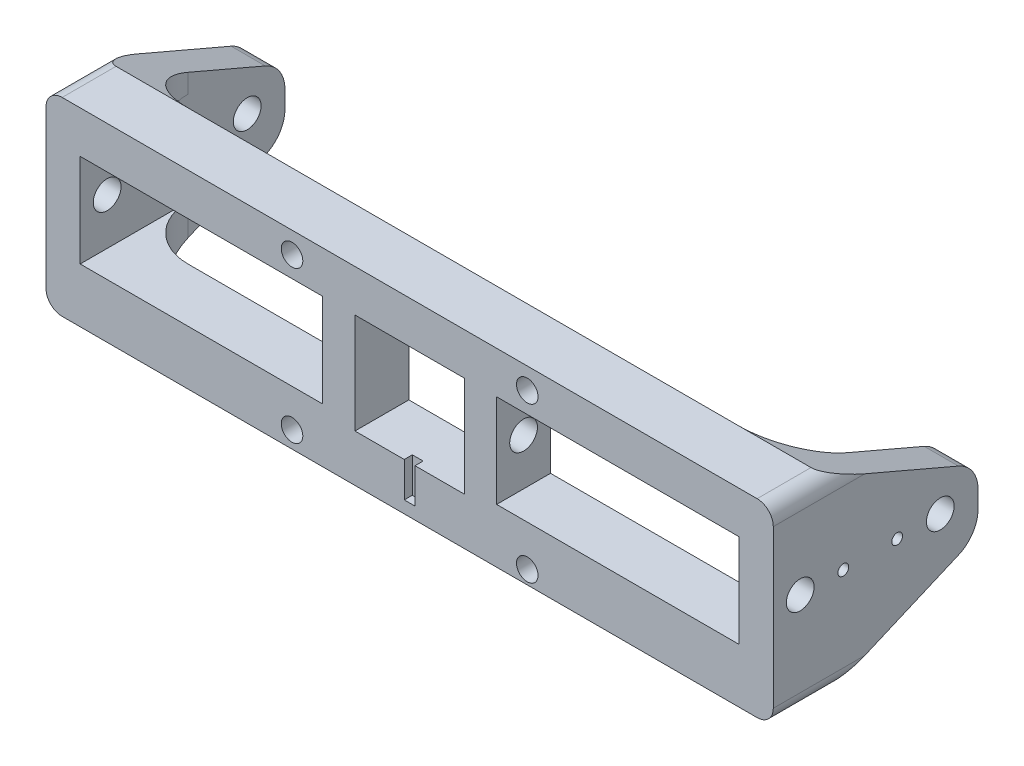
SolidWorks part; units mm, degrees
material "Vero PureWhite"
ref_plane "前视基准面" through (0, 0, 0) normal (0, 0, 1) x (1, 0, 0)
ref_plane "上视基准面" through (0, 0, 0) normal (0, 1, 0) x (1, 0, 0)
ref_plane "右视基准面" through (0, 0, 0) normal (1, 0, 0) x (0, 0, -1)
sketch "草图1" plane through (0, 0, 0) normal (0, 0, 1) x (1, 0, 0)
  line L1 (-67.5, 29) -> (67.5, 29)
  line L2 (-67.5, 29) -> (-67.5, -29)
  line L3 (-67.5, -29) -> (67.5, -29)
  line L4 (67.5, 29) -> (67.5, -29)
  line L5 (-67.5, 29) -> (67.5, -29) construction
  line L6 (-67.5, -29) -> (67.5, 29) construction
  point P0 (0, 0)
  dimension "D1" = 135
  dimension "D2" = 58
extrude "凸台-拉伸1" add sketch "草图1" along normal blind 10
sketch "草图3" plane through (0, 0, 0) normal (0, 0, -1) x (-1, 0, 0)
  line L1 (-10.15, 20.25) -> (10.15, 20.25)
  line L2 (-10.15, 20.25) -> (-10.15, -20.25)
  line L3 (-10.15, -20.25) -> (10.15, -20.25)
  line L4 (10.15, 20.25) -> (10.15, -20.25)
  line L5 (-10.15, 20.25) -> (10.15, -20.25) construction
  line L6 (-10.15, -20.25) -> (10.15, 20.25) construction
  point P0 (0, 0)
  dimension "D1" = 40.5
  dimension "D2" = 20.3
extrude "切除-拉伸1" cut sketch "草图3" against normal blind 20
sketch "草图4" plane through (0, 0, 0) normal (0, 0, -1) x (-1, 0, 0)
  line L0 (0, 0) -> (0, 8.0602) construction
  line L1 (0, 0) -> (3.3984, 0) construction
  circle A0 centre (-5, 24.6) radius 1.525
  circle A1 centre (5, 24.6) radius 1.525
  circle A2 centre (5, -24.6) radius 1.525
  circle A3 centre (-5, -24.6) radius 1.525
  dimension "D1" = 3.05
  dimension "D2" = 5
  dimension "D3" = 24.6
extrude "切除-拉伸2" cut sketch "草图4" against normal blind 20
sketch "草图5" plane through (0, 0, 0) normal (0, 0, -1) x (-1, 0, 0)
  line L0 (-10.15, -20.25) -> (10.15, -20.25) construction
  line L1 (10.15, -20.25) -> (10.15, 20.25) construction
  line L2 (61.15, -17.9) -> (16.15, -17.9)
  line L3 (61.15, -17.9) -> (61.15, -2.6)
  line L4 (61.15, -2.6) -> (16.15, -2.6)
  line L5 (16.15, -17.9) -> (16.15, -2.6)
  line L6 (61.15, -17.9) -> (16.15, -2.6) construction
  line L7 (61.15, -2.6) -> (16.15, -17.9) construction
  line L9 (0, 0) -> (0, -4.0519) construction
  line L10 (-61.15, -2.6) -> (-16.15, -17.9) construction
  line L11 (-61.15, -17.9) -> (-16.15, -2.6) construction
  line L12 (-16.15, -17.9) -> (-16.15, -2.6)
  line L13 (-61.15, -2.6) -> (-16.15, -2.6)
  line L14 (-61.15, -17.9) -> (-61.15, -2.6)
  line L15 (-61.15, -17.9) -> (-16.15, -17.9)
  point P0 (2.5, -10.25)
  point P3 (38.65, -10.25)
  point P17 (-38.65, -10.25)
  dimension "D1" = 10
  dimension "D2" = 45
  dimension "D3" = 6
  dimension "D4" = 15.3
extrude "切除-拉伸3" cut sketch "草图5" against normal blind 20
sketch "草图7" plane through (-67.5, 0, 0) normal (-1, 0, 0) x (0, 0, 1)
  line L0 (10, -17.9) -> (0, -17.9) construction
  line L1 (0, -17.9) -> (0, -2.6) construction
  line L2 (10, -17.9) -> (10, -2.6) construction
  line L3 (10, -2.6) -> (0, -2.6) construction
  line L4 (10, -17.9) -> (0, -17.9) construction
  line L5 (0, -17.9) -> (0, -2.6) construction
  line L6 (10, -17.9) -> (10, -2.6) construction
  line L7 (10, -2.6) -> (0, -2.6) construction
  circle A0 centre (5, -10.25) radius 2.575
  point P6 (5, -2.6)
  point P7 (10, -10.25)
  dimension "D1" = 5.15
extrude "切除-拉伸4" cut sketch "草图7" against normal blind 57
sketch "草图9" plane through (0, 0, 0) normal (0, 0, -1) x (-1, 0, 0)
  line L0 (-16.15, -2.6) -> (-61.15, -2.6) construction
  line L1 (-67.5, 29) -> (-18.15, 29)
  line L2 (-67.5, 29) -> (-67.5, 6.2)
  line L3 (-67.5, 6.2) -> (-18.15, 6.2)
  line L4 (-18.15, 29) -> (-18.15, 6.2)
  line L5 (-10.15, 20.25) -> (-10.15, -20.25) construction
  line L6 (0, 5.5) -> (0, -5.5) construction
  line L7 (18.15, 29) -> (18.15, 6.2)
  line L8 (67.5, 6.2) -> (18.15, 6.2)
  line L9 (67.5, 29) -> (67.5, 6.2)
  line L10 (67.5, 29) -> (18.15, 29)
  dimension "D1" = 8.8
  dimension "D2" = 8
extrude "切除-拉伸6" cut sketch "草图9" against normal blind 48
fillet "圆角1" radius 3 4 edges at (-18.15, 6.2, 5) (-18.15, 29, 5) (18.15, 6.2, 5) (18.15, 29, 5)
fillet "圆角2" radius 3 4 edges at (-67.5, 6.2, 5) (-67.5, -29, 5) (67.5, 6.2, 5) (67.5, -29, 5)
sketch "草图10" plane through (67.5, 0, 0) normal (1, 0, 0) x (0, 0, -1)
  circle A0 centre (-5, -10.25) radius 2.575 construction
  circle A1 centre (-5, -10.25) radius 2.575
extrude "切除-拉伸7" cut sketch "草图10" against normal blind 57
sketch "草图11" plane through (0, 0, 0) normal (0, 0, -1) x (-1, 0, 0)
  line L0 (61.15, 6.2) -> (61.15, -29)
  line L1 (-61.15, 6.2) -> (-61.15, -29)
  line L2 (61.15, -29) -> (64.5, -29)
  line L8 (67.5, -26) -> (67.5, 3.2)
  line L9 (64.5, 6.2) -> (21.15, 6.2)
  line L10 (18.15, 9.2) -> (18.15, 26)
  line L11 (15.15, 29) -> (-15.15, 29)
  line L12 (-18.15, 26) -> (-18.15, 9.2)
  line L13 (-21.15, 6.2) -> (-64.5, 6.2)
  line L14 (-67.5, 3.2) -> (-67.5, -26)
  line L15 (-64.5, -29) -> (64.5, -29)
  line L16 (67.5, -26) -> (67.5, 3.2)
  line L17 (64.5, 6.2) -> (61.15, 6.2)
  line L21 (-61.15, 6.2) -> (-64.5, 6.2)
  line L22 (-67.5, 3.2) -> (-67.5, -26)
  line L23 (-64.5, -29) -> (-61.15, -29)
  arc A8 (67.5, 3.2) -> (64.5, 6.2) centre (64.5, 3.2) ccw
  arc A9 (18.15, 9.2) -> (21.15, 6.2) centre (21.15, 9.2) ccw
  arc A10 (18.15, 26) -> (15.15, 29) centre (15.15, 26) ccw
  arc A11 (-15.15, 29) -> (-18.15, 26) centre (-15.15, 26) ccw
  arc A12 (-21.15, 6.2) -> (-18.15, 9.2) centre (-21.15, 9.2) ccw
  arc A13 (-64.5, 6.2) -> (-67.5, 3.2) centre (-64.5, 3.2) ccw
  arc A14 (-67.5, -26) -> (-64.5, -29) centre (-64.5, -26) ccw
  arc A15 (64.5, -29) -> (67.5, -26) centre (64.5, -26) ccw
  arc A16 (67.5, 3.2) -> (64.5, 6.2) centre (64.5, 3.2) ccw
  arc A21 (-64.5, 6.2) -> (-67.5, 3.2) centre (-64.5, 3.2) ccw
  arc A22 (-67.5, -26) -> (-64.5, -29) centre (-64.5, -26) ccw
  arc A23 (64.5, -29) -> (67.5, -26) centre (64.5, -26) ccw
  dimension "D1" = 0
extrude "凸台-拉伸2" add sketch "草图11" along normal blind 28
sketch "草图12" plane through (-67.5, 0, 0) normal (-1, 0, 0) x (0, 0, 1)
  line L0 (5, -10.25) -> (-21, -10.25) construction
  circle A0 centre (5, -10.25) radius 2.575 construction
  circle A1 centre (5, -10.25) radius 2.575 construction
  circle A2 centre (-21, -10.25) radius 2.575
  dimension "D1" = 26
extrude "切除-拉伸8" cut sketch "草图12" against normal blind 145
sketch "草图13" plane through (-67.5, 0, 0) normal (-1, 0, 0) x (0, 0, 1)
  line L0 (-28, 6.2) -> (-28, -5.8)
  line L1 (-28, -26) -> (-28, 3.2) construction
  line L2 (-28, -5.8) -> (0, 6.2)
  line L3 (0, 6.2) -> (-28, 6.2)
  line L4 (-28, -11.4) -> (-11.8081, -11.4) construction
  line L5 (0, -29) -> (-28, -29)
  line L6 (-28, -17) -> (0, -29)
  line L7 (-28, -29) -> (-28, -17)
  dimension "D1" = 12
  dimension "D2" = 28
extrude "切除-拉伸9" cut sketch "草图13" against normal blind 145
fillet "圆角3" radius 6 4 edges at (-64.325, -17, -28) (-64.325, -5.8, -28) (64.325, -17, -28) (64.325, -5.8, -28)
fillet "圆角4" radius 10 4 edges at (-61.15, -23.45, 0) (-61.15, 1.8, 0) (61.15, -23.45, 0) (61.15, 1.8, 0)
sketch "草图14" plane through (-67.5, 0, 0) normal (-1, 0, 0) x (0, 0, 1)
  circle A0 centre (-13, -10.25) radius 1
  circle A1 centre (-3, -10.25) radius 1
  circle A2 centre (5, -10.25) radius 2.575 construction
  circle A3 centre (-21, -10.25) radius 2.575 construction
  dimension "D4" = 2
  dimension "D1" = 8
  dimension "D2" = 8
  dimension "D3" = 10
extrude "切除-拉伸10" cut sketch "草图14" against normal blind 135
sketch "草图15" plane through (0, 0, 10) normal (0, 0, 1) x (1, 0, 0)
  line L0 (10.15, 20.25) -> (-10.15, 20.25) construction
  line L1 (-1, 26.75) -> (1, 26.75)
  line L2 (-1, 26.75) -> (-1, 13.75)
  line L3 (-1, 13.75) -> (1, 13.75)
  line L4 (1, 26.75) -> (1, 13.75)
  line L5 (-1, 26.75) -> (1, 13.75) construction
  line L6 (-1, 13.75) -> (1, 26.75) construction
  line L7 (20.9, 0) -> (-20.9, 0) construction
  line L8 (-1, -13.75) -> (1, -26.75) construction
  line L9 (-1, -26.75) -> (1, -13.75) construction
  line L10 (1, -26.75) -> (1, -13.75)
  line L11 (-1, -13.75) -> (1, -13.75)
  line L12 (-1, -26.75) -> (-1, -13.75)
  line L13 (-1, -26.75) -> (1, -26.75)
  point P0 (0, 20.25)
  point P13 (0, -20.25)
  dimension "D1" = 2
  dimension "D2" = 13
extrude "切除-拉伸11" cut sketch "草图15" against normal blind 1.5
sketch "草图16" plane through (0, 0, 0) normal (0, 0, -1) x (-1, 0, 0)
  line L0 (-18.15, 9.2) -> (-18.15, 26) construction
  line L1 (-18.15, 20.25) -> (18.15, 20.25)
  line L2 (-18.15, 20.25) -> (-18.15, 26)
  line L3 (-15.15, 29) -> (15.15, 29)
  line L4 (18.15, 20.25) -> (18.15, 26)
  line L5 (18.15, 26) -> (18.15, 9.2) construction
  arc A0 (-15.15, 29) -> (-18.15, 26) centre (-15.15, 26) ccw construction
  arc A1 (-15.15, 29) -> (-18.15, 26) centre (-15.15, 26) ccw
  arc A2 (18.15, 26) -> (15.15, 29) centre (15.15, 26) ccw construction
  arc A3 (18.15, 26) -> (15.15, 29) centre (15.15, 26) ccw
extrude "凸台-拉伸3" add sketch "草图16" along normal blind 10
sketch "草图17" plane through (0, 29, 0) normal (0, 1, 0) x (1, 0, 0)
  line L1 (-9, 6) -> (9, 6) construction
  line L2 (-9, 6) -> (-9, -6) construction
  line L3 (-9, -6) -> (9, -6) construction
  line L4 (9, 6) -> (9, -6) construction
  line L5 (-9, 6) -> (9, -6) construction
  line L6 (-9, -6) -> (9, 6) construction
  circle A0 centre (-9, 6) radius 1.5
  circle A1 centre (9, 6) radius 1.5
  circle A2 centre (9, -6) radius 1.5
  circle A3 centre (-9, -6) radius 1.5
  point P0 (0, 0)
  dimension "D3" = 3
  dimension "D1" = 18
  dimension "D2" = 12
extrude "切除-拉伸12" cut sketch "草图17" against normal blind 8
fillet "圆角6" radius 10 2 edges at (-14.15, 20.25, 0) (14.15, 20.25, 0)
sketch "草图18" plane through (0, 21, 0) normal (0, 1, 0) x (1, 0, 0)
  circle A0 centre (9, 6) radius 1.5 construction
  circle A1 centre (-9, 6) radius 1.5 construction
  circle A2 centre (9, 6) radius 1.5
  circle A3 centre (-9, 6) radius 1.5
extrude "切除-拉伸13" cut sketch "草图18" against normal blind 8
sketch "草图19" plane through (0, -17.9, 0) normal (0, 1, 0) x (1, 0, 0)
  line L0 (16.15, -10) -> (61.15, -10) construction
  line L1 (61.15, -10) -> (61.15, 10) construction
  line L2 (51.15, 0) -> (16.15, 0) construction
  line L3 (16.15, 0) -> (16.15, -10) construction
  line L4 (-61.15, -10) -> (-16.15, -10) construction
  line L5 (-16.15, -10) -> (-16.15, 0) construction
  line L6 (-16.15, 0) -> (-51.15, 0) construction
  line L7 (-61.15, 10) -> (-61.15, -10) construction
  line L8 (16.15, -10) -> (61.15, -10)
  line L9 (61.15, -10) -> (61.15, 10)
  line L10 (51.15, 0) -> (16.15, 0)
  line L11 (16.15, 0) -> (16.15, -10)
  line L12 (-61.15, -10) -> (-16.15, -10)
  line L13 (-16.15, -10) -> (-16.15, 0)
  line L14 (-16.15, 0) -> (-51.15, 0)
  line L15 (-61.15, 10) -> (-61.15, -10)
  arc A0 (51.15, 0) -> (61.15, 10) centre (51.15, 10) ccw construction
  arc A1 (-61.15, 10) -> (-51.15, 0) centre (-51.15, 10) ccw construction
  arc A2 (51.15, 0) -> (61.15, 10) centre (51.15, 10) ccw
  arc A3 (-61.15, 10) -> (-51.15, 0) centre (-51.15, 10) ccw
extrude "切除-拉伸14" cut sketch "草图19" against normal blind 1
sketch "草图20" plane through (0, -2.6, 0) normal (0, -1, 0) x (1, 0, 0)
  line L0 (-16.15, 10) -> (-61.15, 10) construction
  line L1 (-61.15, 10) -> (-61.15, -10) construction
  line L2 (-51.15, 0) -> (-16.15, 0) construction
  line L3 (-16.15, 0) -> (-16.15, 10) construction
  line L4 (61.15, 10) -> (16.15, 10) construction
  line L5 (16.15, 10) -> (16.15, 0) construction
  line L6 (16.15, 0) -> (51.15, 0) construction
  line L7 (61.15, -10) -> (61.15, 10) construction
  line L8 (-16.15, 10) -> (-61.15, 10)
  line L9 (-61.15, 10) -> (-61.15, -10)
  line L10 (-51.15, 0) -> (-16.15, 0)
  line L11 (-16.15, 0) -> (-16.15, 10)
  line L12 (61.15, 10) -> (16.15, 10)
  line L13 (16.15, 10) -> (16.15, 0)
  line L14 (16.15, 0) -> (51.15, 0)
  line L15 (61.15, -10) -> (61.15, 10)
  arc A0 (-51.15, 0) -> (-61.15, -10) centre (-51.15, -10) ccw construction
  arc A1 (61.15, -10) -> (51.15, 0) centre (51.15, -10) ccw construction
  arc A2 (-51.15, 0) -> (-61.15, -10) centre (-51.15, -10) ccw
  arc A3 (61.15, -10) -> (51.15, 0) centre (51.15, -10) ccw
extrude "切除-拉伸15" cut sketch "草图20" against normal blind 1
scale "缩放比例1" scale about origin uniform scaling yes scale factor 0.6
sketch "草图21" plane through (0, 0, 0) normal (0, 0, -1) x (-1, 0, 0)
  line L1 (-17.7657, 30.0859) -> (19.0808, 30.0859)
  line L2 (-17.7657, 30.0859) -> (-17.7657, 0.9885)
  line L3 (-17.7657, 0.9885) -> (19.0808, 0.9885)
  line L4 (19.0808, 30.0859) -> (19.0808, 0.9885)
extrude "切除-拉伸16" cut sketch "草图21" along normal blind 10
other "删除面1" face at (-5.4, 12.6, 4.5) face at (-5.4, 12.6, 4.5) face at (5.4, 12.6, 4.5) face at (5.4, 12.6, 4.5) face at (3.915, 14.76, 6) face at (-2.085, 14.76, 6) face at (-2.085, -14.76, 6) face at (3.915, -14.76, 6) and patch yes
sketch "草图22" plane through (0, 0, 0) normal (0, 0, -1) x (-1, 0, 0)
  line L0 (-30.69, 3.72) -> (-12.69, 3.72) construction
  line L1 (-19.5013, 3.72) -> (22.8183, 3.72)
  line L2 (-19.5013, 3.72) -> (-19.5013, 20.5963)
  line L3 (-19.5013, 20.5963) -> (22.8183, 20.5963)
  line L4 (22.8183, 3.72) -> (22.8183, 20.5963)
extrude "切除-拉伸17" cut sketch "草图22" against normal blind 10
sketch "草图23" plane through (0, 0, 0) normal (0, 0, -1) x (-1, 0, 0)
  line L0 (-6.09, 3.72) -> (-6.09, -12.15) construction
  line L1 (6.09, 3.72) -> (-6.09, 3.72)
  line L2 (6.09, 3.72) -> (6.09, -0.96)
  line L3 (6.09, -0.96) -> (-6.09, -0.96)
  line L4 (-6.09, 3.72) -> (-6.09, -0.96)
  line L5 (-9.69, -0.96) -> (-30.69, -0.96) construction
extrude "凸台-拉伸4" add sketch "草图23" against normal up to surface (6 mm away) up to face at (0, -7.9988, 6)
hole_wizard "M2 六角凹头螺钉的柱形沉头孔1" positions "草图27" profile "草图26" counterbore size "M2" standard "ISO" end condition through all
sketch "草图27" plane through (0, 0, 0) normal (0, 0, -1) x (-1, 0, 0)
  line L4 (30.69, -17.4) -> (-30.69, -17.4) construction
  point P0 (13.1, 1.355)
  point P2 (-13.1, 1.355)
  point P13 (-13.1, -15.9)
  point P19 (13.1, -15.5388)
  dimension "D5" = 1.5
sketch "草图26" plane through (-13.1, 1.355, 0) normal (1, 0, 0) x (0, 1, 0)
  line L0 (0, 0) -> (0, 6)
  line L1 (0, 6) -> (1.2, 6)
  line L3 (1.2, 6) -> (1.2, 2.4)
  line L4 (1.2, 2.4) -> (2.2, 2.4)
  line L5 (2.2, 2.4) -> (2.2, 0)
  line L7 (2.2, 0) -> (0, 0)
  line L11 (0, -6.35) -> (0, 107.95) construction
  dimension "通孔孔直径" = 2.4
  dimension "通孔孔深度" = 6
  dimension "柱形沉头孔直径" = 4.4
  dimension "柱形沉头孔深度" = 2.4
sketch "草图28" plane through (0, 0, 0) normal (0, 0, -1) x (-1, 0, 0)
  line L1 (-15.3, -15.9) -> (-10.9, -15.9)
  line L2 (-15.3, -15.9) -> (-15.3, -19.8253)
  line L3 (-15.3, -19.8253) -> (-10.9, -19.8253)
  line L4 (-10.9, -15.9) -> (-10.9, -19.8253)
  line L5 (10.9, -15.5388) -> (15.3, -15.5388)
  line L6 (10.9, -15.5388) -> (10.9, -19.8253)
  line L7 (10.9, -19.8253) -> (15.3, -19.8253)
  line L8 (15.3, -15.5388) -> (15.3, -19.8253)
  arc A0 (-11.4907, -17.4) -> (-14.7093, -17.4) centre (-13.1, -15.9) ccw construction
  arc A1 (-11.4907, -17.4) -> (-14.7093, -17.4) centre (-13.1, -15.9) ccw construction
  arc A2 (14.273, -17.4) -> (11.927, -17.4) centre (13.1, -15.5388) ccw construction
  arc A3 (14.273, -17.4) -> (11.927, -17.4) centre (13.1, -15.5388) ccw construction
extrude "切除-拉伸18" cut sketch "草图28" against normal up to surface (2.4 mm away) up to face at (11.9, -15.9, 2.4)
